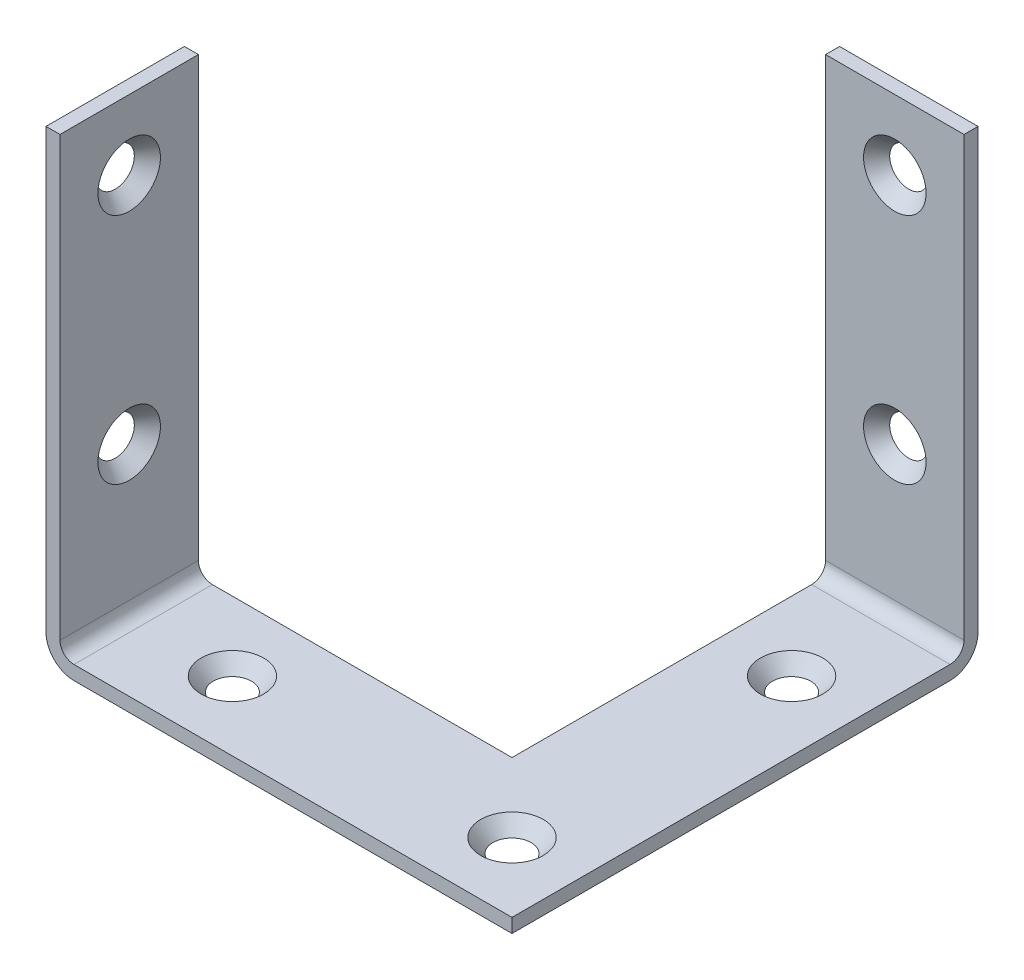
SolidWorks part; units mm, degrees
ref_plane "Front" through (0, 0, 0) normal (0, 0, 1) x (1, 0, 0)
ref_plane "Top" through (0, 0, 0) normal (0, 1, 0) x (1, 0, 0)
ref_plane "Right" through (0, 0, 0) normal (1, 0, 0) x (0, 0, -1)
sketch "Sketch1" plane through (0, 0, 0) normal (0, 0, 1) x (1, 0, 0)
  line L0 (-50.8, 50.8) -> (-50.8, 3.048)
  line L1 (-47.752, 0) -> (0, 0)
  arc A0 (-47.752, 0) -> (-50.8, 3.048) centre (-47.752, 3.048) cw
  point P6 (-50.8, 0)
  dimension "D1" = 3.048
  dimension "A1" = 50.8
  dimension "A2" = 50.8
extrude "Extrude-Thin1" add sketch "Sketch1" against normal mid plane 15.0876 thin thin type one direction reverse wall 1.524
sketch "Sketch4" plane through (0, 1.524, 0) normal (0, 1, 0) x (1, 0, 0)
  line L0 (-38.0238, 0) -> (-7.5438, 0) construction
  line L2 (-47.752, 7.5438) -> (0, 7.5438) construction
  line L3 (0, 7.5438) -> (0, -7.5438) construction
  circle A0 centre (-7.5438, 0) radius 2.0828
  circle A1 centre (-38.0238, 0) radius 2.0828
  circle A2 centre (-7.5438, 0) radius 7.5438 construction
  dimension "Hole Size" = 4.1656
  dimension "Hole Offset H 2" = 30.48
extrude "Cut-Extrude1" cut sketch "Sketch4" against normal through all
sketch "Sketch5" plane through (-49.276, 0, 0) normal (1, 0, 0) x (0, 0, -1)
  line L1 (0, 43.18) -> (0, 17.78) construction
  line L2 (7.5438, 50.8) -> (-7.5438, 50.8) construction
  circle A0 centre (0, 43.18) radius 2.0828
  circle A1 centre (0, 17.78) radius 2.0828
  dimension "D1" = 4.1656
  dimension "Hole Offset V 2" = 25.4
  dimension "Hole Offset V 1" = 7.62
extrude "Cut-Extrude2" cut sketch "Sketch5" against normal through all
chamfer "Chamfer1" distance 1.524 angle 41 4 edges at (-49.276, 45.2628, 0) (-49.276, 19.8628, 0) (-38.0238, 1.524, 2.0828) (-7.5438, 1.524, 2.0828) first distance on face at (-50.8, 45.2628, 0) first distance on face at (-50.8, 19.8628, 0) first distance on face at (-38.0238, 0, 2.0828) first distance on face at (-7.5438, 0, 2.0828)
ref_axis "Axis2" through (-7.5438, 1.524, 0) along (0, -1, 0)
pattern_circular "CirPattern1" count 2 over 90 about axis through (-7.5438, 1.524, 0) along (0, -1, 0) of bodies 112 108
combine bodies "Combine1" operation type add bodies to combine 109 112
equation "\"D1@Sketch1\" = \"Thickness@Extrude-Thin1\" * 2"
equation "\"D1@Sketch5\" = \"Hole Size@Sketch4\""
